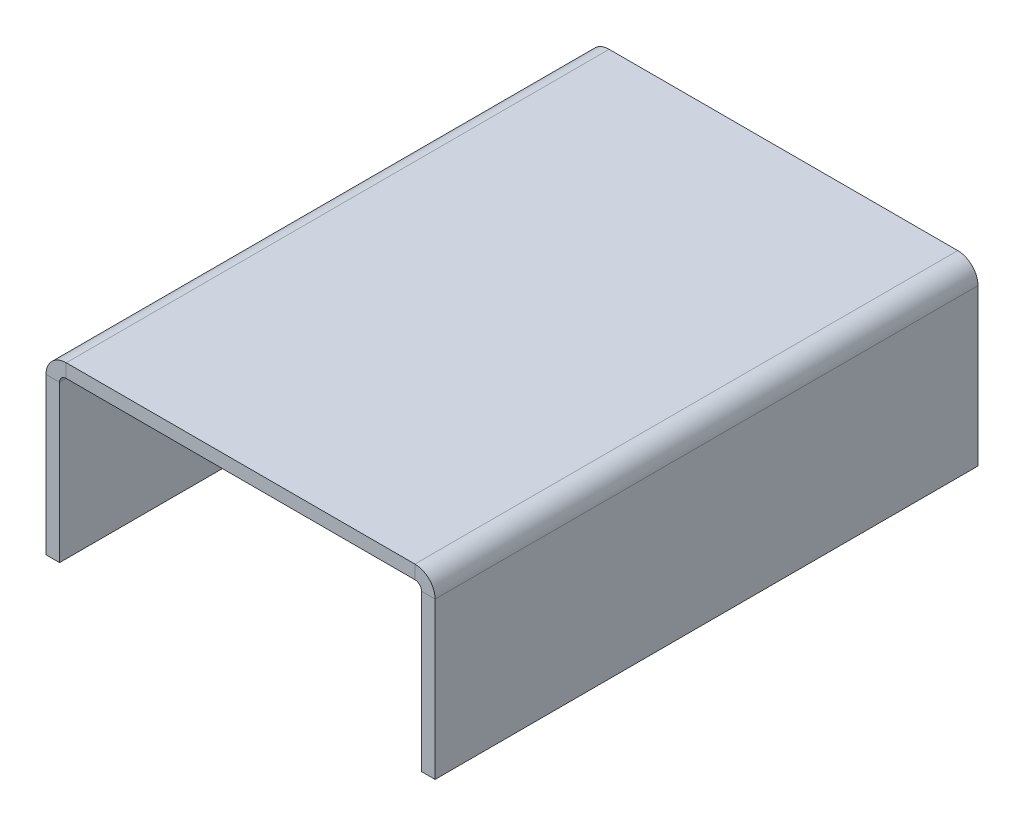
SolidWorks part; units mm, degrees
note: The reader was unsure of these and kept them because the rebuilt part matched: bend radius of "Base-Flange1", "BaseBend1", "BaseBend2".
ref_plane "Front Plane" through (0, 0, 0) normal (0, 0, 1) x (1, 0, 0)
ref_plane "Top Plane" through (0, 0, 0) normal (0, 1, 0) x (1, 0, 0)
ref_plane "Right Plane" through (0, 0, 0) normal (1, 0, 0) x (0, 0, -1)
sketch "Sketch1" plane through (0, 0, 0) normal (0, 0, 1) x (1, 0, 0)
  line L2 (-20, -9) -> (-20, 9)
  line L3 (-20, 9) -> (20, 9)
  line L4 (20, -9) -> (20, 9)
  line L5 (-20, -9) -> (20, 9) construction
  line L6 (-20, 9) -> (20, -9) construction
  point P0 (0, 0)
  dimension "D1" = 40
  dimension "D2" = 18
base flange "Base-Flange1" sketch "Sketch1" end condition mid plane depth 60 reverse direction no thickness 1.5 reverse thickness direction no bend radius 0.7366
bend "BaseBend1" bend radius 0.7366 bend angle 90 parameters "D5"=1
bend "BaseBend2" bend radius 0.7366 bend angle 90 parameters "D5"=2
sketch "Bend-Lines1" [suppressed] plane through (0, 0, 0) normal (0, 1, 0) x (1, 0, 0)
sketch "Bounding-Box1" [suppressed] plane through (0, 0, 0) normal (0, 1, 0) x (1, 0, 0)
sheet metal parameters "Sheet-Metal1" thickness 1.5 parameters "D1"=0.7366
flat pattern "Flat-Pattern1" [suppressed]
sketch "Bend-Lines2" plane through (0, 9, 0) normal (0, -1, 0) x (-1, 0, 0)
  line L0 (20.431, 30) -> (20.431, -30) construction
  line L1 (-20.431, -30) -> (-20.431, 30) construction
  line L2 (20.431, 30) -> (20.431, -30) construction
  line L3 (-20.431, -30) -> (-20.431, 30) construction
sketch3d "Bounding-Box2" [suppressed]
  line L0 (-58.8619, 60, 0) -> (18.8619, 60, 0) construction
  line L1 (-58.8619, 0, 0) -> (18.8619, 0, 0) construction
  line L2 (-58.8619, 60, 0) -> (-58.8619, 0, 0) construction
  line L3 (18.8619, 60, 0) -> (18.8619, 0, 0) construction
bend of the flat pattern "Flatten-<BaseBend1>1"
bend of the flat pattern "Flatten-<BaseBend2>1"
